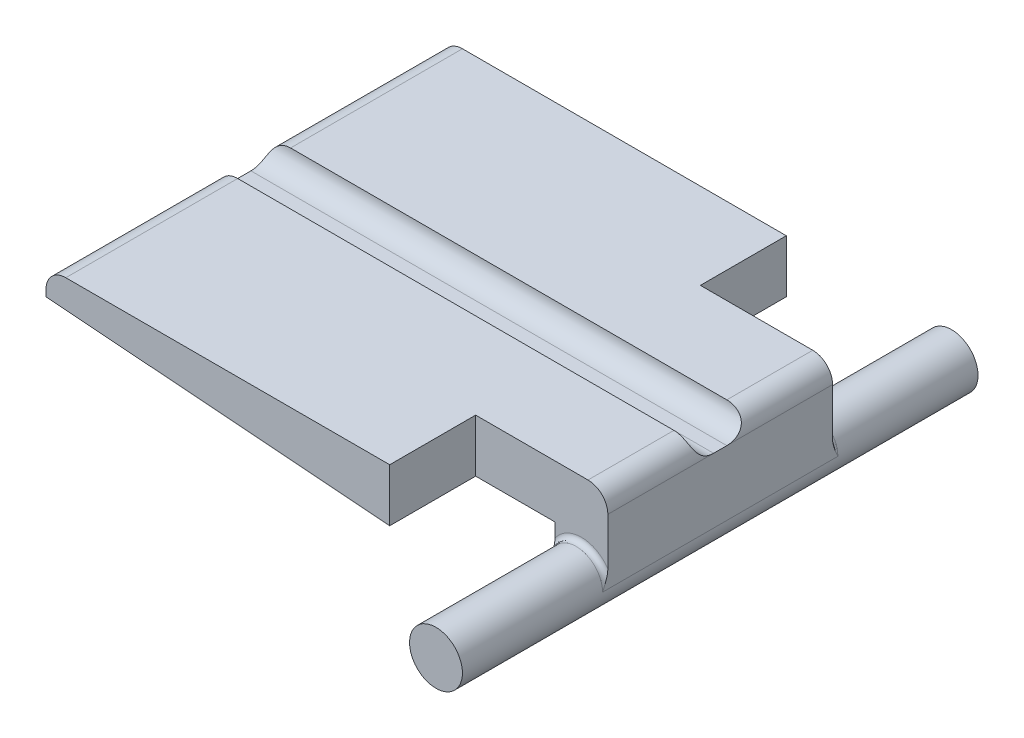
SolidWorks part; units mm, degrees
ref_plane "Front Plane" through (0, 0, 0) normal (0, 0, 1) x (1, 0, 0)
ref_plane "Top Plane" through (0, 0, 0) normal (0, 1, 0) x (1, 0, 0)
ref_plane "Right Plane" through (0, 0, 0) normal (1, 0, 0) x (0, 0, -1)
sketch "Sketch1" plane through (0, 0, 0) normal (0, 1, 0) x (1, 0, 0)
  line L0 (6.5, 4.25) -> (11.5, 4.25)
  line L1 (-6.5, -7.5) -> (6.5, -7.5)
  line L2 (-6.5, -7.5) -> (-6.5, 7.5)
  line L3 (-6.5, 7.5) -> (6.5, 7.5)
  line L4 (6.5, -7.5) -> (6.5, -4.25)
  line L5 (-6.5, -7.5) -> (6.5, 7.5) construction
  line L6 (-6.5, 7.5) -> (6.5, -7.5) construction
  line L10 (11.5, 4.25) -> (11.5, -4.25)
  line L13 (6.5, 4.25) -> (6.5, 7.5)
  line L17 (6.5, -4.25) -> (11.5, -4.25)
  point P0 (0, 0)
  point P6 (11.5, 0)
  dimension "D1" = 15
  dimension "D2" = 13
  dimension "D3" = 8.5
  dimension "D4" = 5
extrude "Boss-Extrude1" add sketch "Sketch1" along normal blind 2
sketch "Sketch2" plane through (0, 2, 0) normal (0, 1, 0) x (1, 0, 0)
  line L1 (-12.5, 1) -> (12.5, 1)
  line L2 (-12.5, 1) -> (-12.5, -1)
  line L3 (-12.5, -1) -> (12.5, -1)
  line L4 (12.5, 1) -> (12.5, -1)
  line L5 (-12.5, 1) -> (12.5, -1) construction
  line L6 (-12.5, -1) -> (12.5, 1) construction
  point P0 (0, 0)
  dimension "D1" = 25
  dimension "D2" = 2
extrude "Cut-Extrude1" cut sketch "Sketch2" against normal blind 0.75
sketch "Sketch3" plane through (0, 0, 0) normal (0, -1, 0) x (1, 0, 0)
  line L0 (11.5, -4.25) -> (6.5, -4.25) construction
  line L1 (11.5, 4.25) -> (9.5, 4.25)
  line L2 (11.5, 4.25) -> (11.5, -4.25)
  line L3 (11.5, -4.25) -> (9.5, -4.25)
  line L4 (9.5, 4.25) -> (9.5, -4.25)
  dimension "D1" = 2
extrude "Boss-Extrude2" add sketch "Sketch3" along normal blind 1.2
sketch "Sketch4" plane through (0, 0, 0) normal (0, 0, 1) x (1, 0, 0)
  line L0 (11.5, -1.2) -> (9.5, -1.2) construction
  circle A0 centre (10.5, -1.2) radius 1
extrude "Boss-Extrude3" add sketch "Sketch4" along normal mid plane 19.5
fillet "Fillet1" radius 0.75 2 edges at (2.5, 1.25, -1) (2.5, 1.25, 1)
fillet "Fillet2" radius 0.75 4 edges at (11.5, 2, -2.625) (11.5, 2, 2.625) (-6.5, 2, -4.25) (-6.5, 2, 4.25)
chamfer "Chamfer1" distance 13 distance2 1 1 edges at (-6.5, 0, 0) first distance on face at (4, 0, 0)
fillet "Fillet3" radius 0.2 2 edges at (10.5, -0.2, 4.25) (10.5, -0.2, -4.25)
